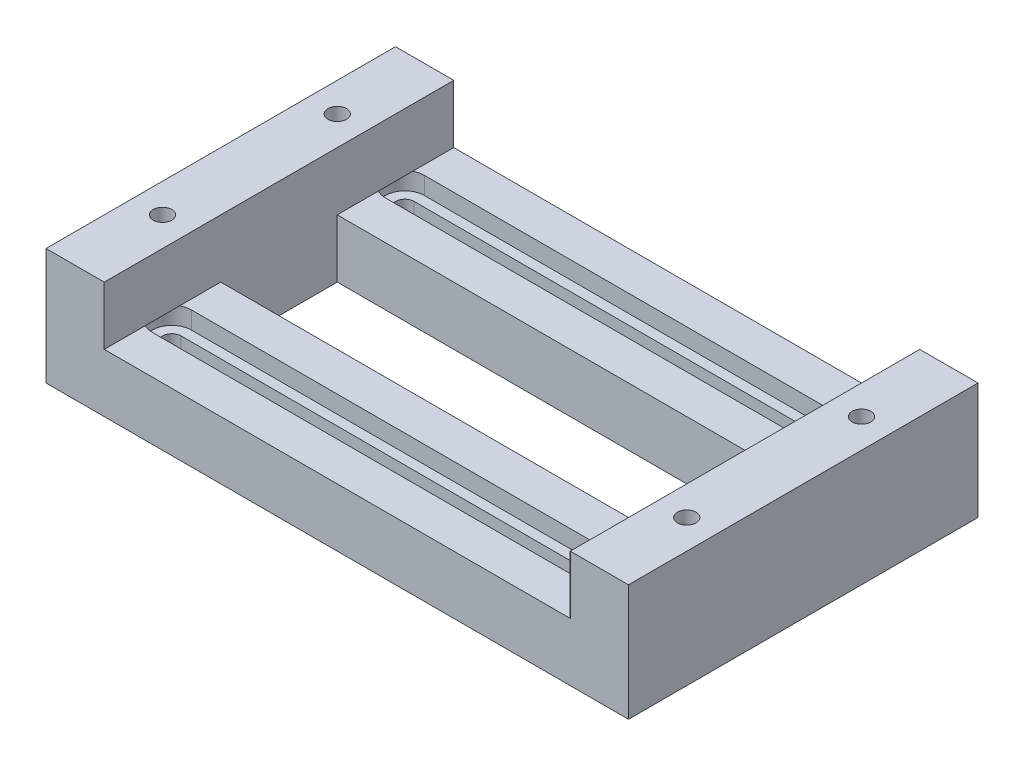
SolidWorks part; units mm, degrees
ref_plane "Front Plane" through (0, 0, 0) normal (0, 0, 1) x (1, 0, 0)
ref_plane "Top Plane" through (0, 0, 0) normal (0, 1, 0) x (1, 0, 0)
ref_plane "Right Plane" through (0, 0, 0) normal (1, 0, 0) x (0, 0, -1)
sketch "Sketch1" plane through (0, 0, 0) normal (0, 1, 0) x (1, 0, 0)
  line L0 (10, 40) -> (10, 20)
  line L1 (0, 0) -> (100, 0)
  line L2 (0, 0) -> (0, 60)
  line L3 (0, 60) -> (100, 60)
  line L4 (100, 0) -> (100, 60)
  line L5 (10, 20) -> (90, 20)
  line L6 (90, 20) -> (90, 40)
  line L7 (90, 40) -> (10, 40)
  line L8 (11.6, 10) -> (88.4, 10) construction
  line L9 (11.6, 11.6) -> (88.4, 11.6)
  line L10 (11.6, 8.4) -> (88.4, 8.4)
  line L11 (88.4, 50) -> (11.6, 50) construction
  line L12 (88.4, 48.4) -> (11.6, 48.4)
  line L13 (50, 0) -> (50, 20) construction
  line L14 (50, 40) -> (50, 60)
  line L15 (88.4, 51.6) -> (11.6, 51.6)
  circle A7 centre (5, 45) radius 1.6
  arc A22 (11.6, 11.6) -> (11.6, 8.4) centre (11.6, 10) ccw
  arc A23 (88.4, 8.4) -> (88.4, 11.6) centre (88.4, 10) ccw
  arc A24 (88.4, 48.4) -> (88.4, 51.6) centre (88.4, 50) ccw
  arc A25 (11.6, 51.6) -> (11.6, 48.4) centre (11.6, 50) ccw
  circle A29 centre (5, 15) radius 1.6
  circle A46 centre (95, 45) radius 1.6
  circle A47 centre (95, 15) radius 1.6
  point P14 (50, 50)
  point P17 (50, 10)
  point P22 (50, 50)
  point P33 (50, 10)
  point P34 (90, 10)
  point P35 (10, 10)
  point P36 (90, 50)
  point P37 (10, 50)
  dimension "D25" = 3.2
  dimension "D4" = 3.2
  dimension "D18" = 3.2
  dimension "D19" = 3.2
  dimension "D1" = 60
  dimension "D2" = 100
  dimension "D3" = 10
  dimension "D22" = 20
  dimension "D23" = 20
  dimension "D24" = 10
  dimension "D28" = 15
  dimension "D5" = 15
  dimension "D6" = 5
  dimension "D8" = 5
  dimension "D9" = 15
  dimension "D13" = 5
  dimension "D16" = 5
  dimension "D17" = 15
  dimension "D7" = 3.2
  dimension "D10" = 3.2
  dimension "D11" = 80
  dimension "D12" = 80
extrude "Boss-Extrude1" add sketch "Sketch1" along normal blind 10 contours L1 L4 L3 L2 A47 A46 A29 A7 L7 L6 L5 L0 region at (75, 0, -58.8338)
sketch "Sketch3" plane through (0, 10, 0) normal (0, 1, 0) x (1, 0, 0)
  line L4 (88.4, 53.35) -> (11.6, 53.35)
  line L5 (11.6, 46.65) -> (88.4, 46.65)
  line L6 (88.4, 13.35) -> (11.6, 13.35)
  line L7 (11.6, 6.65) -> (88.4, 6.65)
  line L8 (88.4, 13.35) -> (11.6, 13.35)
  line L9 (11.6, 6.65) -> (88.4, 6.65)
  line L10 (88.4, 53.35) -> (11.6, 53.35)
  line L11 (11.6, 46.65) -> (88.4, 46.65)
  arc A4 (88.4, 46.65) -> (88.4, 53.35) centre (88.4, 50) ccw
  arc A5 (11.6, 53.35) -> (11.6, 46.65) centre (11.6, 50) ccw
  arc A6 (11.6, 13.35) -> (11.6, 6.65) centre (11.6, 10) ccw
  arc A7 (88.4, 6.65) -> (88.4, 13.35) centre (88.4, 10) ccw
  arc A8 (11.6, 13.35) -> (11.6, 6.65) centre (11.6, 10) ccw
  arc A9 (88.4, 6.65) -> (88.4, 13.35) centre (88.4, 10) ccw
  arc A10 (88.4, 46.65) -> (88.4, 53.35) centre (88.4, 50) ccw
  arc A11 (11.6, 53.35) -> (11.6, 46.65) centre (11.6, 50) ccw
  dimension "D1" = 1.75
  dimension "D2" = 1.75
extrude "Cut-Slot insets" cut sketch "Sketch3" against normal blind 3
sketch "Sketch5" plane through (0, 10, 0) normal (0, 1, 0) x (1, 0, 0)
  line L2 (0, 60) -> (100, 60) construction
  line L3 (10, 60) -> (0, 60)
  line L4 (0, 60) -> (0, 0)
  line L5 (0, 0) -> (10, 0)
  line L6 (0, 0) -> (100, 0) construction
  line L9 (90, 0) -> (100, 0)
  line L10 (100, 0) -> (100, 60)
  line L11 (100, 60) -> (90, 60)
  line L20 (90, 60) -> (90, 0)
  line L21 (90, 20) -> (90, 40) construction
  line L22 (10, 0) -> (10, 60)
  line L23 (10, 40) -> (10, 20) construction
  circle A0 centre (95, 45) radius 1.6
  circle A3 centre (95, 15) radius 1.6
  circle A5 centre (5, 15) radius 1.6
  circle A8 centre (5, 45) radius 1.6
  circle A9 centre (5, 15) radius 1.6 construction
  circle A10 centre (5, 45) radius 1.6 construction
  circle A11 centre (95, 45) radius 1.6 construction
  circle A12 centre (95, 15) radius 1.6 construction
extrude "Boss-Extrude3" add sketch "Sketch5" along normal blind 10
sketch "Sketch6" plane through (0, 0, 0) normal (0, -1, 0) x (1, 0, 0)
  circle A0 centre (5, -45) radius 3.75
  circle A2 centre (5, -15) radius 3.75
  circle A3 centre (95, -15) radius 3.75
  circle A5 centre (95, -45) radius 3.75
  dimension "D1" = 7.5
  dimension "D3" = 7.5
  dimension "D4" = 7.5
  dimension "D6" = 7.5
extrude "Cut-Extrude1" cut sketch "Sketch6" against normal blind 2.5
chamfer "Chamfer1" distance 0.5 angle 45 8 edges at (50, 0, -51.6) (90, 0, -50) (10, 0, -50) (50, 0, -48.4) (50, 0, -8.4) (10, 0, -10) (90, 0, -10) (50, 0, -11.6)
equation "\"boltdiameter\"=3.2"
equation "\"D25@Sketch1\"=\"boltdiameter\""
equation "\"D4@Sketch1\"=\"boltdiameter\""
equation "\"D18@Sketch1\"=\"boltdiameter\""
equation "\"D19@Sketch1\"=\"boltdiameter\""
equation "\"boltfacediameter\"=7"
equation "\"boltFaceOffset\"= 1.75"
equation "\"D1@Sketch3\" = \"boltFaceOffset\""
equation "\"D2@Sketch3\" = \"boltFaceOffset\""
equation "\"screwInset\"=7.5"
equation "\"D1@Sketch6\"=\"screwInset\""
equation "\"D3@Sketch6\"=\"screwInset\""
equation "\"D4@Sketch6\"=\"screwInset\""
equation "\"D6@Sketch6\"=\"screwInset\""
equation "\"D7@Sketch1\"=\"boltdiameter\""
equation "\"D10@Sketch1\"=\"boltdiameter\""
equation "\"slotLength\"=80"
equation "\"D11@Sketch1\"=\"slotLength\""
equation "\"D12@Sketch1\"=\"slotLength\""
